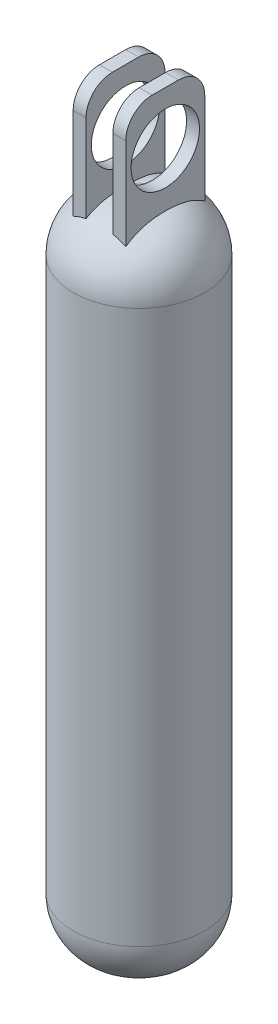
SolidWorks part; units mm, degrees
ref_plane "Front Plane" through (0, 0, 0) normal (0, 0, 1) x (1, 0, 0)
ref_plane "Top Plane" through (0, 0, 0) normal (0, 1, 0) x (1, 0, 0)
ref_plane "Right Plane" through (0, 0, 0) normal (1, 0, 0) x (0, 0, -1)
sketch "Sketch1" plane through (0, 0, 0) normal (0, 1, 0) x (1, 0, 0)
  circle A0 centre (0, 0) radius 2.5
  dimension "D1" = 5
extrude "Boss-Extrude1" add sketch "Sketch1" along normal blind 25
sketch "Sketch2" plane through (0, 25, 0) normal (0, 1, 0) x (1, 0, 0)
  line L0 (-0.5, 1) -> (-0.5, -1)
  line L1 (1, 1.5) -> (-1, 1.5)
  line L2 (1, 1.5) -> (1, -1.5)
  line L3 (1, -1.5) -> (-1, -1.5)
  line L4 (-1, 1.5) -> (-1, -1.5)
  line L5 (1, 1.5) -> (-1, -1.5) construction
  line L6 (1, -1.5) -> (-1, 1.5) construction
  line L7 (0.5, -1) -> (-0.5, -1)
  line L8 (0.5, 1) -> (0.5, -1)
  line L9 (0.5, 1) -> (-0.5, 1)
  point P0 (0, 0)
  dimension "D1" = 2
  dimension "D2" = 3
  dimension "D3" = 0.5
extrude "Boss-Extrude2" add sketch "Sketch2" along normal blind 4
sketch "Sketch3" plane through (0, 29, 0) normal (0, 1, 0) x (1, 0, 0)
  line L1 (0.5095, 1.6146) -> (-0.5095, 1.6146)
  line L2 (0.5095, 1.6146) -> (0.5095, -1.6146)
  line L3 (0.5095, -1.6146) -> (-0.5095, -1.6146)
  line L4 (-0.5095, 1.6146) -> (-0.5095, -1.6146)
  line L5 (0.5095, 1.6146) -> (-0.5095, -1.6146) construction
  line L6 (0.5095, -1.6146) -> (-0.5095, 1.6146) construction
  point P0 (0, 0)
extrude "Cut-Extrude1" cut sketch "Sketch3" against normal blind 4
sketch "Sketch4" plane through (-1, 0, 0) normal (-1, 0, 0) x (0, 0, 1)
  line L0 (0, 29) -> (0, 27)
  line L1 (-1.5, 29) -> (1.5, 29) construction
  circle A0 centre (0, 27) radius 1.3
extrude "Cut-Extrude2" cut sketch "Sketch4" against normal blind 4 contours A0 region at (-1, 26.1068, -0.8932)
fillet "Fillet1" radius 1 4 edges at (0.7548, 29, 1.5) (0.7548, 29, -1.5) (-0.7548, 29, -1.5) (-0.7548, 29, 1.5)
fillet "Fillet2" radius 2 2 edges at (0, 25, 2.5) (0, 0, 2.5)
